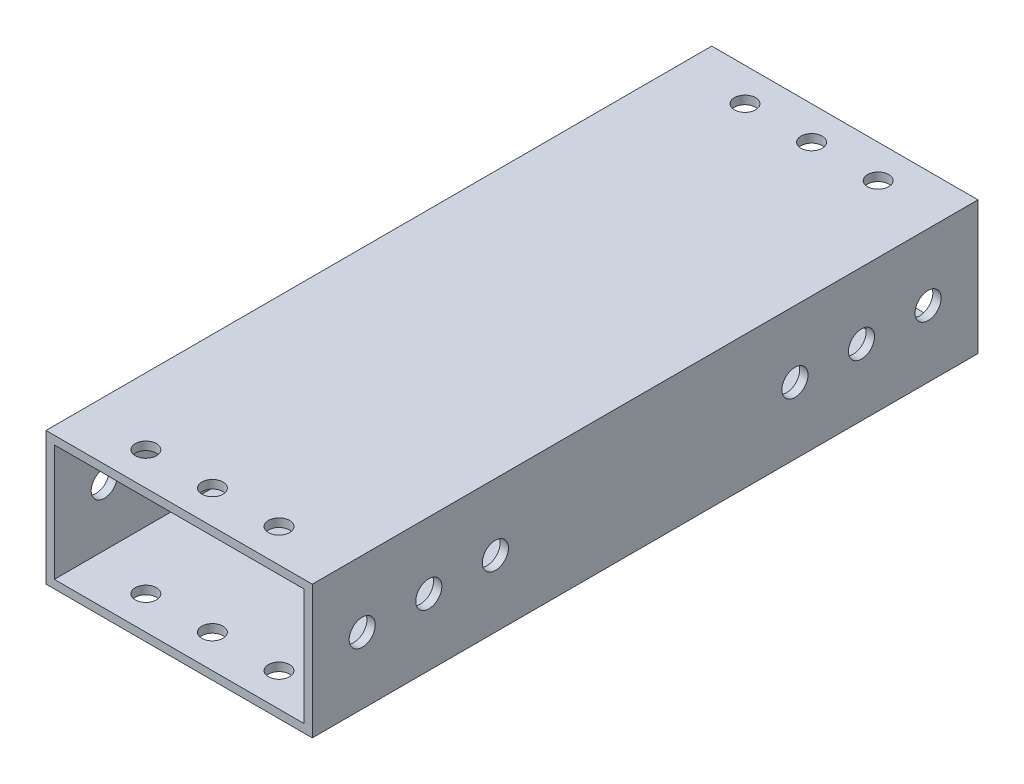
SolidWorks part; units mm, degrees
material "6061-T6 (SS)"
ref_plane "Front Plane" through (0, 0, 0) normal (0, 0, 1) x (1, 0, 0)
ref_plane "Top Plane" through (0, 0, 0) normal (0, 1, 0) x (1, 0, 0)
ref_plane "Right Plane" through (0, 0, 0) normal (1, 0, 0) x (0, 0, -1)
sketch "Sketch1" plane through (0, 0, 0) normal (0, 0, 1) x (1, 0, 0)
  line L0 (-23.8125, 11.1125) -> (23.8125, 11.1125)
  line L1 (-25.4, -12.7) -> (25.4, -12.7)
  line L2 (-25.4, -12.7) -> (-25.4, 12.7)
  line L3 (-25.4, 12.7) -> (25.4, 12.7)
  line L4 (25.4, -12.7) -> (25.4, 12.7)
  line L5 (-25.4, -12.7) -> (25.4, 12.7) construction
  line L6 (-25.4, 12.7) -> (25.4, -12.7) construction
  line L7 (23.8125, -11.1125) -> (23.8125, 11.1125)
  line L8 (-23.8125, -11.1125) -> (23.8125, -11.1125)
  line L9 (-23.8125, -11.1125) -> (-23.8125, 11.1125)
  point P0 (0, 0)
  dimension "D1" = 50.8
  dimension "D2" = 25.4
  dimension "D3" = 1.5875
extrude "Boss-Extrude1" add sketch "Sketch1" along normal mid plane 127
sketch "Sketch2" plane through (0, 12.7, 0) normal (0, 1, 0) x (1, 0, 0)
  line L0 (25.4, 63.5) -> (-25.4, 63.5) construction
  line L1 (25.4, 0) -> (-25.4, 0) construction
  line L2 (25.4, -63.5) -> (25.4, 63.5) construction
  line L3 (-25.4, -63.5) -> (-25.4, 63.5) construction
  circle A0 centre (-12.7, 57.15) radius 2.0193
  circle A1 centre (0, 57.15) radius 2.0193
  circle A2 centre (12.7, 57.15) radius 2.0193
  circle A3 centre (12.7, -57.15) radius 2.0193
  circle A4 centre (0, -57.15) radius 2.0193
  circle A5 centre (-12.7, -57.15) radius 2.0193
  dimension "D1" = 4.0386
  dimension "D2" = 12.7
  dimension "D3" = 12.7
  dimension "D4" = 6.35
extrude "Cut-Extrude1" cut sketch "Sketch2" against normal through all
sketch "Sketch3" plane through (25.4, 0, 0) normal (1, 0, 0) x (0, 0, -1)
  line L0 (0, 12.7) -> (0, -12.7) construction
  line L1 (-63.5, 12.7) -> (63.5, 12.7) construction
  line L2 (-63.5, -12.7) -> (63.5, -12.7) construction
  line L3 (-63.5, -12.7) -> (-63.5, 12.7) construction
  circle A0 centre (-53.975, 0) radius 2.4892
  circle A1 centre (53.975, 0) radius 2.4892
  circle A2 centre (-41.275, 0) radius 2.4892
  circle A3 centre (-28.575, 0) radius 2.4892
  circle A4 centre (28.575, 0) radius 2.4892
  circle A5 centre (41.275, 0) radius 2.4892
  dimension "D3" = 4.9784
  dimension "D2" = 9.525
  dimension "D4" = 12.7
  dimension "D5" = 12.7
extrude "Cut-Extrude2" cut sketch "Sketch3" against normal through all
